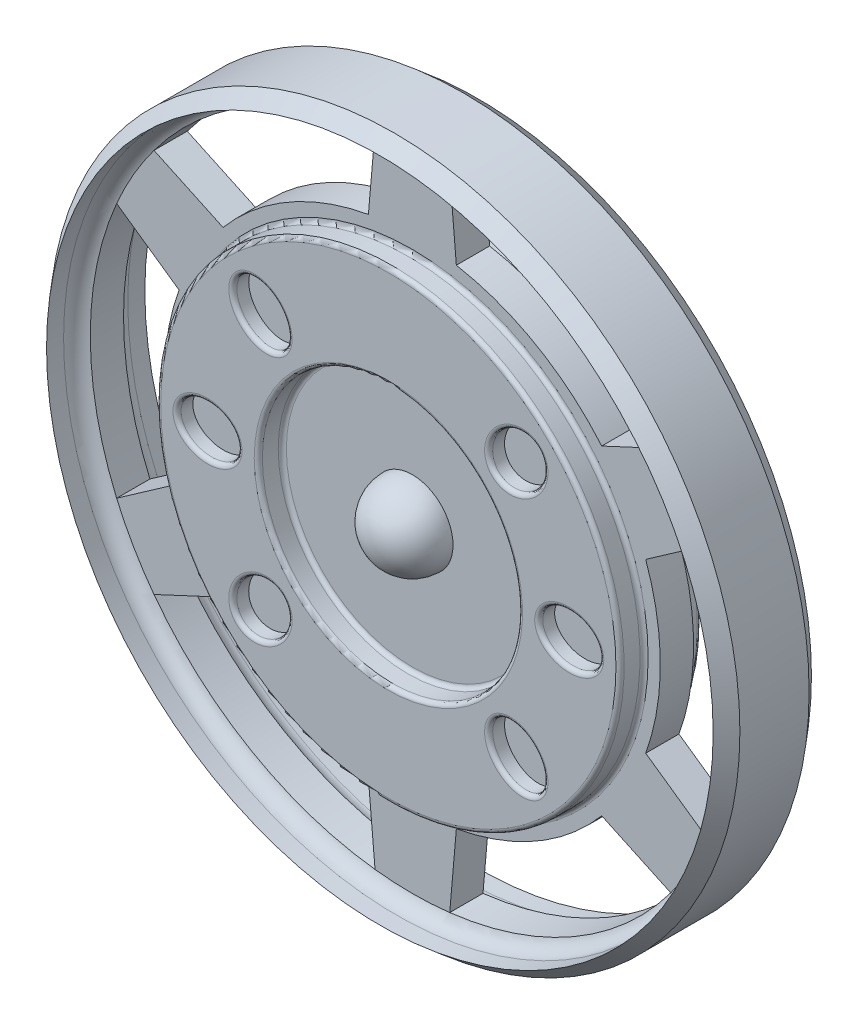
SolidWorks part; units mm, degrees
material "AISI 1020"
ref_plane "Front Plane" through (0, 0, 0) normal (0, 0, 1) x (1, 0, 0)
ref_plane "Top Plane" through (0, 0, 0) normal (0, 1, 0) x (1, 0, 0)
ref_plane "Right Plane" through (0, 0, 0) normal (1, 0, 0) x (0, 0, -1)
sketch "Sketch1" plane through (0, 0, 0) normal (1, 0, 0) x (0, 0, -1)
  line L0 (0, 0) -> (0, 107.95) construction
  line L1 (10.8147, 107.95) -> (-10.8147, 107.95)
  line L2 (-10.8147, 107.95) -> (-15.3552, 104.14)
  line L3 (-15.3552, 104.14) -> (-10.0255, 104.14)
  line L4 (-5.1952, 100.6332) -> (-5.1952, 72.39)
  line L5 (-5.1952, 72.39) -> (-12.7, 72.39)
  line L6 (-12.7, 72.39) -> (-12.7, 40.64)
  line L7 (-12.7, 40.64) -> (-5.1952, 40.64)
  line L8 (-5.1952, 40.64) -> (-5.1952, 12.7)
  line L9 (-17.8952, 0) -> (17.8952, 0)
  line L10 (5.1952, 40.64) -> (5.1952, 12.7)
  line L11 (12.7, 40.64) -> (5.1952, 40.64)
  line L12 (12.7, 72.39) -> (12.7, 40.64)
  line L13 (5.1952, 72.39) -> (12.7, 72.39)
  line L14 (5.1952, 100.6332) -> (5.1952, 72.39)
  line L15 (15.3552, 104.14) -> (10.0255, 104.14)
  line L16 (10.8147, 107.95) -> (15.3552, 104.14)
  arc A0 (-10.0255, 104.14) -> (-5.1952, 100.6332) centre (-10.0255, 99.06) cw
  arc A1 (-5.1952, 12.7) -> (-17.8952, 0) centre (-5.1952, 0) ccw
  arc A2 (5.1952, 12.7) -> (17.8952, 0) centre (5.1952, 0) cw
  arc A3 (10.0255, 104.14) -> (5.1952, 100.6332) centre (10.0255, 99.06) ccw
  point P27 (-8.9476, 40.64)
  dimension "D8" = 12.7
  dimension "D9" = 5.08
  dimension "D1" = 107.95
  dimension "D2" = 25.4
  dimension "D3" = 3.81
  dimension "D4" = 40
  dimension "D5" = 10.16
  dimension "D6" = 31.75
  dimension "D7" = 40.64
revolve "Revolve1" add sketch "Sketch1" angle 360 about L9
sketch "Sketch2" plane through (0, 0, 5.1952) normal (0, 0, 1) x (1, 0, 0)
  line L0 (0, 0) -> (-100.6332, 0) construction
  line L1 (-92.3969, -39.8731) -> (-72.898, -26.2199)
  line L2 (-92.3969, 39.8731) -> (-72.898, 26.2199)
  circle A0 centre (0, 0) radius 100.6332 construction
  arc A1 (-92.3969, 39.8731) -> (-92.3969, -39.8731) centre (0, 0) ccw
  circle A4 centre (0, 0) radius 77.47
  arc A5 (-72.898, 26.2199) -> (-72.898, -26.2199) centre (0, 0) ccw
  dimension "D2" = 70
  dimension "D3" = 72.898
  dimension "D1" = 5.08
extrude "Cut-Extrude1" cut sketch "Sketch2" against normal through all both and the other way through all
pattern_circular "CirPattern1" count 6 over 360 about axis through (0, 0, 0) along (0, 0, 1) of "Cut-Extrude1"
sketch "Sketch3" plane through (0, 0, 12.7) normal (0, 0, 1) x (1, 0, 0)
  line L0 (-40.64, 0) -> (-72.39, 0) construction
  line L1 (0, 0) -> (-39.9621, 39.9621) construction
  circle A0 centre (0, 0) radius 56.515 construction
  circle A1 centre (0, 0) radius 72.39 construction
  circle A2 centre (0, 0) radius 40.64 construction
  circle A3 centre (0, 0) radius 40.64 construction
  ellipse E0 centre (-39.9621, 39.9621) end of major axis (-46.6973, 46.6973) minor radius 7.62
  point P12 (-56.515, 0)
  dimension "D1" = 45
  dimension "D2" = 15.24
  dimension "D3" = 19.05
extrude "Cut-Extrude2" cut sketch "Sketch3" against normal offset from surface (4.9648 mm away) 2.54 up to face at (12.7, 0, 5.1952)
pattern_circular "CirPattern2" count 8 over 360 about axis through (0, 0, 5.1952) along (0, 0, 1) skipping 3, 7 of "Cut-Extrude2"
mirror "Mirror1" about plane through (0, 0, 0) normal (0, 0, 1) of "CirPattern2", "Cut-Extrude2"
fillet "Fillet3" radius 1.27 10 edges at (72.39, 0, 12.7) (40.64, 0, 12.7) (-33.2269, 33.2269, 12.7) (-33.2269, -33.2269, 12.7) (33.2269, -33.2269, 12.7) (46.99, 0, 12.7) (33.2269, 33.2269, 12.7) (-46.99, 0, 12.7) (72.39, 0, 5.1952) (40.64, 0, 5.1952)
fillet "Fillet4" radius 1.27 10 edges at (40.64, 0, -5.1952) (40.64, 0, -12.7) (72.39, 0, -12.7) (72.39, 0, -5.1952) (33.2269, 33.2269, -12.7) (46.99, 0, -12.7) (33.2269, -33.2269, -12.7) (-33.2269, -33.2269, -12.7) (-46.99, 0, -12.7) (-33.2269, 33.2269, -12.7)
equation "\"A\" = 4.25"
equation "\"B\" = 1"
equation "\"C\" = 70"
equation "\"D\" = 2.87"
equation "\"E\" = 45"
equation "\"F\" = .75"
equation "\"D1@Sketch1\"= \"A\""
equation "\"D2@Sketch1\"=\"B\""
equation "\"D2@Sketch2\"=\"C\""
equation "\"D3@Sketch2\"=\"D\""
equation "\"D1@Sketch3\"=\"E\""
equation "\"D3@Sketch3\"=\"F\""
